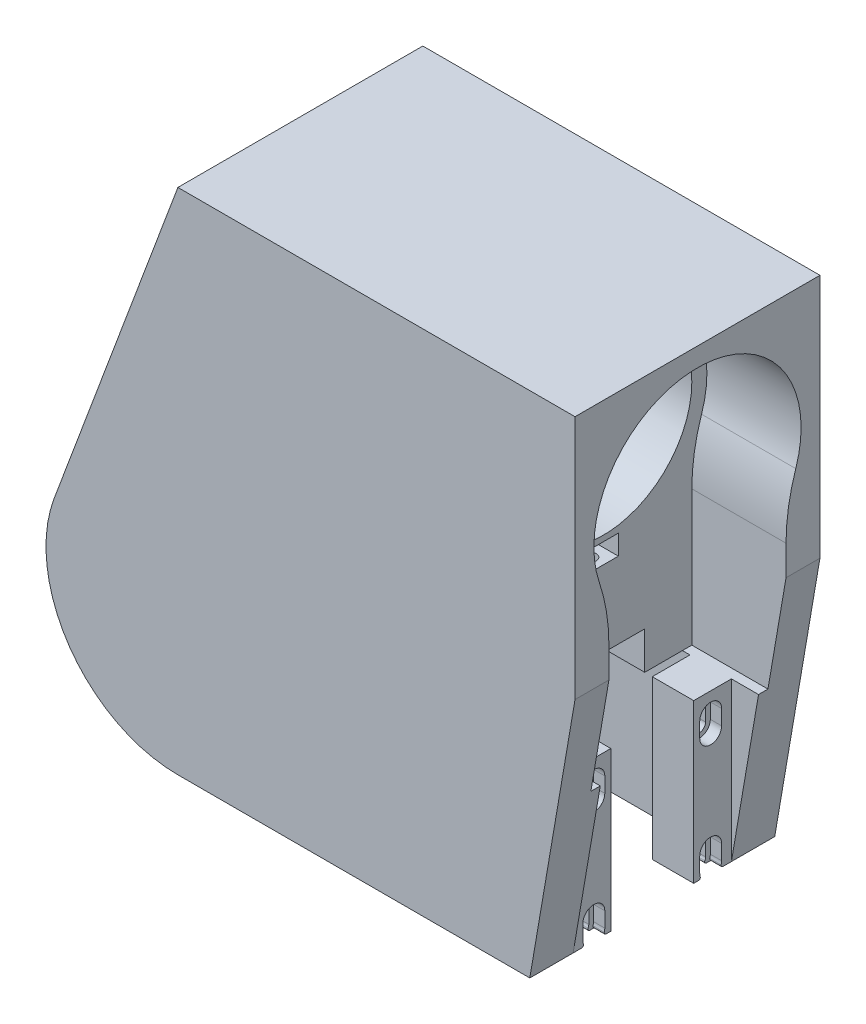
SolidWorks part; units mm, degrees
ref_plane "Ebene vorne" through (0, 0, 0) normal (0, 0, 1) x (1, 0, 0)
ref_plane "Ebene oben" through (0, 0, 0) normal (0, 1, 0) x (1, 0, 0)
ref_plane "Ebene rechts" through (0, 0, 0) normal (1, 0, 0) x (0, 0, -1)
sketch "Skizze1" plane through (0, 0, 0) normal (0, 0, 1) x (1, 0, 0)
  line L0 (0, -35) -> (6.4333, -35) construction
  line L1 (0, -35) -> (40.3912, -35)
  line L2 (82.3912, -35) -> (40.3912, -35)
  line L3 (82.3912, -35) -> (82.3912, 7)
  line L4 (82.3912, 7) -> (40.3912, 7)
  line L5 (40.3912, -35) -> (40.3912, 7)
  line L6 (82.3912, -35) -> (40.3912, 7) construction
  line L7 (82.3912, 7) -> (40.3912, -35) construction
  line L8 (40.3912, -35) -> (82.3912, -35)
  line L9 (40.3912, -35) -> (40.3912, -26.8814)
  line L12 (82.3912, -35) -> (93.3912, -35)
  line L14 (105.3912, 35) -> (93.3912, -35)
  line L15 (82.3912, 7) -> (0, 7)
  line L16 (82.3912, 7) -> (82.3912, 35)
  line L17 (82.3912, 35) -> (0, 35)
  line L18 (0, 7) -> (0, 35)
  line L19 (82.3912, 7) -> (0, 35) construction
  line L20 (82.3912, 35) -> (0, 7) construction
  line L21 (0, 35) -> (105.3912, 35)
  line L22 (0, 35) -> (0, 100)
  line L23 (0, 100) -> (105.3912, 100)
  line L24 (105.3912, 35) -> (105.3912, 100)
  line L25 (0, 35) -> (105.3912, 100) construction
  line L26 (0, 100) -> (105.3912, 35) construction
  line L27 (82.3912, 35) -> (93.3912, 35)
  line L28 (82.3912, 35) -> (82.3912, -35)
  line L30 (93.3912, 35) -> (93.3912, -35)
  line L31 (82.3912, 35) -> (93.3912, -35) construction
  line L32 (88.7388, -5.3941) -> (93.3912, 35) construction
  line L33 (0, 100) -> (-32.7862, 12.25)
  line L35 (105.3912, 35) -> (71.3912, 35)
  line L36 (105.3912, 35) -> (105.3912, 100)
  line L37 (105.3912, 100) -> (71.3912, 100)
  line L38 (71.3912, 35) -> (71.3912, 100)
  line L39 (105.3912, 35) -> (71.3912, 100) construction
  line L40 (105.3912, 100) -> (71.3912, 35) construction
  circle A0 centre (0, 0) radius 35
  point P10 (61.3912, -23.5)
  point P15 (41.1956, 21)
  point P19 (52.6956, 67.5)
  point P22 (88.7388, -5.3941)
  point P26 (88.3912, 67.5)
  dimension "D1" = 70
  dimension "D2" = 42
  dimension "D3" = 42
  dimension "D4" = 11
  dimension "D5" = 65
  dimension "D6" = 12
  dimension "D8" = 34
extrude "Aufsatz-Linear austragen1" add sketch "Skizze1" along normal blind 65
sketch "Skizze2" plane through (105.3912, 0, 0) normal (1, 0, 0) x (0, 0, -1)
  line L0 (-32.5, 100) -> (-32.5, -35) construction
  line L1 (-65, 100) -> (0, 100) construction
  line L4 (-53.5, 7) -> (-11.5, 7)
  line L5 (-53.5, 7) -> (-53.5, -35)
  line L6 (-53.5, -35) -> (-11.5, -35)
  line L7 (-11.5, 7) -> (-11.5, -35)
  line L8 (-53.5, 7) -> (-11.5, -35) construction
  line L9 (-53.5, -35) -> (-11.5, 7) construction
  line L13 (-65, -35) -> (0, -35) construction
  point P6 (-32.5, -14)
  dimension "D1" = 42
  dimension "D3" = 42
extrude "Schnitt-Linear austragen1" cut sketch "Skizze2" against normal up to vertex (12 mm away)
sketch "Skizze3" plane through (105.3912, 0, 0) normal (1, 0, 0) x (0, 0, -1)
  line L0 (0, 35) -> (0, 100) construction
  line L1 (-65, 100) -> (0, 100)
  line L2 (-65, 100) -> (-65, 35)
  line L3 (-65, 35) -> (0, 35)
  line L4 (0, 100) -> (0, 35)
  line L5 (-65, 100) -> (0, 35) construction
  line L6 (-65, 35) -> (0, 100) construction
  line L7 (0, 35) -> (0, -35) construction
  circle A0 centre (-32.5, 67.5) radius 15
  point P4 (-32.5, 67.5)
  dimension "D1" = 30
extrude "Schnitt-Linear austragen2" cut sketch "Skizze3" against normal blind 147 contours A0
ref_plane "Ebene1" through (-20.6088, 0, 0) normal (-1, 0, 0) x (0, 0, 1)
sketch "Skizze5" plane through (-20.6088, 0, 0) normal (-1, 0, 0) x (0, 0, 1)
  circle A0 centre (32.5, 67.5) radius 23.5
  dimension "D1" = 47
extrude "Schnitt-Linear austragen3" cut sketch "Skizze5" against normal blind 46 and the other way blind 3
sketch "Skizze6" plane through (25.3912, 0, 0) normal (-1, 0, 0) x (0, 0, 1)
  circle A0 centre (32.5, 67.5) radius 20
  dimension "D1" = 40
extrude "Schnitt-Linear austragen4" cut sketch "Skizze6" against normal blind 5
sketch "Skizze8" plane through (105.3912, 0, 0) normal (1, 0, 0) x (0, 0, -1)
  circle A0 centre (-32.5, 67.5) radius 23.5
  dimension "D1" = 47
extrude "Schnitt-Linear austragen5" cut sketch "Skizze8" against normal blind 37
sketch "Skizze9" plane through (68.3912, 0, 0) normal (1, 0, 0) x (0, 0, -1)
  circle A0 centre (-32.5, 67.5) radius 20
  dimension "D1" = 40
extrude "Schnitt-Linear austragen6" cut sketch "Skizze9" against normal blind 5
sketch "Skizze10" plane through (0, 0, 0) normal (0, 0, -1) x (-1, 0, 0)
  circle A0 centre (0, 0) radius 15
  circle A1 centre (0, 0) radius 7
  dimension "D1" = 30
  dimension "D2" = 14
extrude "Schnitt-Linear austragen7" cut sketch "Skizze10" against normal offset from surface (47.5 mm away) 17.5 contours A1 up to face at (43.1708, 28.112, 65)
sketch "Skizze11" plane through (0, 100, 0) normal (0, 1, 0) x (1, 0, 0)
  line L1 (7, -17.5) -> (-7, -17.5)
  line L2 (7, -17.5) -> (7, -47.5)
  line L3 (7, -47.5) -> (-7, -47.5)
  line L4 (-7, -17.5) -> (-7, -47.5)
  line L5 (7, -17.5) -> (-7, -47.5) construction
  line L6 (7, -47.5) -> (-7, -17.5) construction
  line L7 (0, -65) -> (0, 0) construction
  point P4 (0, -32.5)
  point P8 (0, -32.5)
  dimension "D1" = 14
  dimension "D2" = 30
extrude "Schnitt-Linear austragen8" cut sketch "Skizze11" against normal blind 65 from offset 34 offset against normal yes
ref_plane "Ebene2" through (-35, 0, 0) normal (-1, 0, 0) x (0, 0, 1)
sketch "Skizze12" plane through (-35, 0, 0) normal (-1, 0, 0) x (0, 0, 1)
  line L0 (32.5, 67.5) -> (32.5, -35) construction
  line L2 (65, -35) -> (0, -35) construction
  line L3 (9.75, 11.25) -> (55.25, 11.25)
  line L4 (9.75, 11.25) -> (9.75, -11.25)
  line L5 (9.75, -11.25) -> (55.25, -11.25)
  line L6 (55.25, 11.25) -> (55.25, -11.25)
  line L7 (9.75, 11.25) -> (55.25, -11.25) construction
  line L8 (9.75, -11.25) -> (55.25, 11.25) construction
  point P5 (32.5, 0)
  dimension "D1" = 22.5
  dimension "D2" = 45.5
extrude "Schnitt-Linear austragen9" cut sketch "Skizze12" against normal blind 4
sketch "Skizze13" plane through (-31, 0, 0) normal (-1, 0, 0) x (0, 0, 1)
  line L0 (9.75, 11.25) -> (55.25, 11.25) construction
  line L1 (17.5, 8.75) -> (47.5, 8.75)
  line L2 (17.5, 8.75) -> (17.5, -8.75)
  line L3 (17.5, -8.75) -> (47.5, -8.75)
  line L4 (47.5, 8.75) -> (47.5, -8.75)
  line L5 (17.5, 8.75) -> (47.5, -8.75) construction
  line L6 (17.5, -8.75) -> (47.5, 8.75) construction
  point P0 (32.5, 0)
  point P9 (32.5, 11.25)
  dimension "D1" = 30
  dimension "D2" = 17.5
extrude "Schnitt-Linear austragen10" cut sketch "Skizze13" against normal blind 31
sketch "Skizze14" plane through (105.3912, 0, 0) normal (1, 0, 0) x (0, 0, -1)
  line L0 (-11.5, 7) -> (-53.5, 7) construction
  line L1 (-56, 67.5) -> (-9, 67.5)
  line L2 (-56, 67.5) -> (-56, 7)
  line L3 (-56, 7) -> (-9, 7)
  line L4 (-9, 67.5) -> (-9, 7)
  line L5 (-56, 67.5) -> (-9, 7) construction
  line L6 (-56, 7) -> (-9, 67.5) construction
  circle A0 centre (-32.5, 67.5) radius 23.5 construction
  circle A1 centre (-32.5, 67.5) radius 23.5 construction
  point P4 (-32.5, 37.25)
extrude "Schnitt-Linear austragen11" cut sketch "Skizze14" against normal offset from surface (25 mm away) 12 up to face at (68.3912, 67.5, 12.5)
sketch "Skizze19" plane through (93.3912, 0, 0) normal (1, 0, 0) x (0, 0, -1)
  line L1 (-53.5, 7) -> (-11.5, 7)
  line L2 (-53.5, 7) -> (-53.5, -35)
  line L3 (-53.5, -35) -> (-11.5, -35)
  line L4 (-11.5, 7) -> (-11.5, -35)
  line L5 (-53.5, 7) -> (-11.5, -35) construction
  line L6 (-53.5, -35) -> (-11.5, 7) construction
  line L7 (-43.5, -35) -> (-21.5, -35)
  line L8 (-43.5, -35) -> (-43.5, 7)
  line L9 (-43.5, 7) -> (-21.5, 7)
  line L10 (-21.5, -35) -> (-21.5, 7)
  line L11 (-43.5, -35) -> (-21.5, 7) construction
  line L12 (-43.5, 7) -> (-21.5, -35) construction
  point P4 (-32.5, -14)
  point P7 (-32.5, -14)
  dimension "D1" = 22
extrude "Schnitt-Linear austragen17" cut sketch "Skizze19" against normal blind 11 contours L3 L10 L1 L8
sketch "Skizze20" plane through (82.3912, 0, 0) normal (1, 0, 0) x (0, 0, -1)
  line L0 (-21.5, -35) -> (-21.5, 7) construction
  line L1 (-53.5, 7) -> (-11.5, 7)
  line L2 (-53.5, 7) -> (-53.5, -35)
  line L3 (-53.5, -35) -> (-11.5, -35)
  line L4 (-11.5, 7) -> (-11.5, -35)
  line L5 (-53.5, 7) -> (-11.5, -35) construction
  line L6 (-53.5, -35) -> (-11.5, 7) construction
  line L7 (-43.5, 7) -> (-21.5, 7)
  line L8 (-43.5, 7) -> (-43.5, 17)
  line L9 (-43.5, 17) -> (-21.5, 17)
  line L10 (-21.5, 7) -> (-21.5, 17)
  line L11 (-43.5, 7) -> (-21.5, 17) construction
  line L12 (-43.5, 17) -> (-21.5, 7) construction
  point P4 (-32.5, -14)
  point P11 (-32.5, 12)
  dimension "D1" = 10
extrude "Schnitt-Linear austragen18" cut sketch "Skizze20" against normal blind 40
sketch "Skizze21" plane through (42.3912, 0, 0) normal (1, 0, 0) x (0, 0, -1)
  line L1 (-43.5, 17) -> (-21.5, 17)
  line L2 (-43.5, 17) -> (-43.5, 7)
  line L3 (-43.5, 7) -> (-21.5, 7)
  line L4 (-21.5, 17) -> (-21.5, 7)
  line L5 (-43.5, 17) -> (-21.5, 7) construction
  line L6 (-43.5, 7) -> (-21.5, 17) construction
  point P4 (-32.5, 12)
extrude "Schnitt-Linear austragen19" cut sketch "Skizze21" against normal up to surface (35.3912 mm away) up to face at (7, 23.8525, 32.5)
sketch "Skizze22" plane through (93.3912, 0, 0) normal (1, 0, 0) x (0, 0, -1)
  line L0 (-48, 1.5) -> (-17, 1.5) construction
  line L1 (-53.5, 7) -> (-11.5, 7)
  line L2 (-53.5, 7) -> (-53.5, -35)
  line L3 (-53.5, -35) -> (-11.5, -35)
  line L4 (-11.5, 7) -> (-11.5, -35)
  line L5 (-53.5, 7) -> (-11.5, -35) construction
  line L6 (-53.5, -35) -> (-11.5, 7) construction
  line L7 (-48, 1.5) -> (-48, -2.5) construction
  line L8 (-46.35, 1.5) -> (-46.35, -2.5)
  line L9 (-49.65, 1.5) -> (-49.65, -2.5)
  line L10 (-32.5, -14) -> (-32.5, -10.696) construction
  line L11 (-17, 1.5) -> (-17, -2.5) construction
  line L12 (-18.65, 1.5) -> (-18.65, -2.5)
  line L13 (-15.35, 1.5) -> (-15.35, -2.5)
  line L14 (-49.65, -29.5) -> (-49.65, -33.5)
  line L15 (-46.35, -29.5) -> (-46.35, -33.5)
  line L16 (-18.65, -29.5) -> (-18.65, -33.5)
  line L17 (-15.35, -29.5) -> (-15.35, -33.5)
  line L18 (-48, -29.5) -> (-48, -33.5) construction
  line L19 (-17, -29.5) -> (-17, -33.5) construction
  arc A0 (-46.35, 1.5) -> (-49.65, 1.5) centre (-48, 1.5) ccw
  arc A1 (-49.65, -2.5) -> (-46.35, -2.5) centre (-48, -2.5) ccw
  arc A2 (-18.65, 1.5) -> (-15.35, 1.5) centre (-17, 1.5) cw
  arc A3 (-15.35, -2.5) -> (-18.65, -2.5) centre (-17, -2.5) cw
  arc A4 (-46.35, -29.5) -> (-49.65, -29.5) centre (-48, -29.5) ccw
  arc A5 (-49.65, -33.5) -> (-46.35, -33.5) centre (-48, -33.5) ccw
  arc A6 (-15.35, -33.5) -> (-18.65, -33.5) centre (-17, -33.5) cw
  arc A7 (-18.65, -29.5) -> (-15.35, -29.5) centre (-17, -29.5) cw
  point P4 (-32.5, -14)
  point P9 (-48, -0.5)
  point P18 (-17, -0.5)
  point P27 (-48, -31.5)
  point P34 (-17, -31.5)
  dimension "D2" = 2
  dimension "D1" = 31
extrude "Schnitt-Linear austragen20" cut sketch "Skizze22" against normal up to surface (11 mm away) contours L9 A1 L8 A0 | A3 L13 A2 L12 | A7 L16 A6 L3 L17 | L14 A5 L3 L15 A4
sketch "Skizze23" plane through (93.3912, 0, 0) normal (1, 0, 0) x (0, 0, -1)
  line L0 (-48, 1.5) -> (-48, -2.5) construction
  line L1 (-45.1, 1.5) -> (-45.1, -2.5)
  line L2 (-50.9, 1.5) -> (-50.9, -2.5)
  line L3 (-32.5, 7) -> (-32.5, -35) construction
  line L5 (-53.5, -35) -> (-11.5, -35) construction
  line L6 (-17, 1.5) -> (-17, -2.5) construction
  line L7 (-19.9, 1.5) -> (-19.9, -2.5)
  line L8 (-14.1, 1.5) -> (-14.1, -2.5)
  line L9 (-50.9, -29.5) -> (-50.9, -33.5)
  line L10 (-45.1, -29.5) -> (-45.1, -33.5)
  line L11 (-19.9, -29.5) -> (-19.9, -33.5)
  line L12 (-14.1, -29.5) -> (-14.1, -33.5)
  line L13 (-48, -29.5) -> (-48, -33.5) construction
  line L14 (-17, -29.5) -> (-17, -33.5) construction
  line L15 (-43.5, 7) -> (-21.5, 7) construction
  arc A0 (-45.1, 1.5) -> (-50.9, 1.5) centre (-48, 1.5) ccw
  arc A1 (-50.9, -2.5) -> (-45.1, -2.5) centre (-48, -2.5) ccw
  arc A2 (-19.9, 1.5) -> (-14.1, 1.5) centre (-17, 1.5) cw
  arc A3 (-14.1, -2.5) -> (-19.9, -2.5) centre (-17, -2.5) cw
  arc A4 (-45.1, -29.5) -> (-50.9, -29.5) centre (-48, -29.5) ccw
  arc A5 (-50.9, -33.5) -> (-45.1, -33.5) centre (-48, -33.5) ccw
  arc A6 (-14.1, -33.5) -> (-19.9, -33.5) centre (-17, -33.5) cw
  arc A7 (-19.9, -29.5) -> (-14.1, -29.5) centre (-17, -29.5) cw
  point P4 (-48, -0.5)
  point P17 (-17, -0.5)
  point P22 (0, 0)
  point P26 (-48, -31.5)
  point P33 (-17, -31.5)
  dimension "D1" = 2
extrude "Schnitt-Linear austragen21" cut sketch "Skizze23" against normal blind 3
fillet "Verrundung2" radius 0.5 8 edges at (86.3912, -35, 47.3126) (86.3912, -35, 48.6874) (86.3912, -35, 16.3126) (86.3912, -35, 17.6874) (91.8912, -35, 45.5181) (91.8912, -35, 50.4819) (91.8912, -35, 14.5181) (91.8912, -35, 19.4819)
sketch "Skizze24" plane through (0, 0, 0) normal (0, 0, -1) x (-1, 0, 0)
  line L0 (0, 7) -> (0, 15) construction
  circle A0 centre (0, 0) radius 7
  circle A1 centre (0, 0) radius 15
  circle A2 centre (0, 11) radius 2.25
  circle A3 centre (11, 0) radius 2.25
  circle A4 centre (0, -11) radius 2.25
  circle A5 centre (-11, 0) radius 2.25
  point P20 (0, 0)
  dimension "D1" = 30
  dimension "D2" = 4.5
  dimension "D4" = 14
  dimension "D3" = 4
extrude "Schnitt-Linear austragen22" cut sketch "Skizze24" against normal blind 15
sketch "Skizze25" plane through (-31, 0, 0) normal (-1, 0, 0) x (0, 0, 1)
  line L0 (9.75, 7.2787) -> (16.75, 7.2787) construction
  line L1 (9.75, 11.2787) -> (55.25, 11.2787)
  line L2 (9.75, 11.2787) -> (9.75, -11.25)
  line L3 (9.75, -11.25) -> (55.25, -11.25)
  line L4 (55.25, 11.2787) -> (55.25, -11.25)
  line L5 (9.75, 11.2787) -> (55.25, -11.25) construction
  line L6 (9.75, -11.25) -> (55.25, 11.2787) construction
  line L8 (32.5, 0.0143) -> (32.5, 2.7471) construction
  line L9 (32.5, 2.7471) -> (32.5, 0.0143) construction
  line L10 (32.5, 0.0143) -> (28.5274, 0.0143) construction
  circle A0 centre (13.25, 7.2787) radius 2.25
  circle A1 centre (13.25, -7.25) radius 2.25
  circle A2 centre (51.75, -7.25) radius 2.25
  circle A3 centre (51.75, 7.2787) radius 2.25
  point P4 (32.5, 0.0143)
  point P9 (16.1306, 7.2787)
  point P10 (16.5813, 7.2787)
  point P22 (0, 0)
  point P23 (17, 7.2787)
  dimension "D1" = 4.5
  dimension "D2" = 4
  dimension "D3" = 3.5
extrude "Schnitt-Linear austragen23" cut sketch "Skizze25" against normal blind 5 contours A0 | A3 | A2 | A1
sketch "Skizze26" plane through (-32.7862, 12.25, 0) normal (-0.9367, 0.35, 0) x (0, 0, 1)
  line L0 (32.5, 46.8375) -> (32.5, 53.1519) construction
  line L1 (0, 93.675) -> (65, 93.675)
  line L2 (0, 93.675) -> (0, 0)
  line L3 (0, 0) -> (65, 0)
  line L4 (65, 93.675) -> (65, 0)
  line L5 (0, 93.675) -> (65, 0) construction
  line L6 (0, 0) -> (65, 93.675) construction
  line L7 (32.5, 53.1519) -> (32.5, 46.8375) construction
  line L8 (32.5, 46.8375) -> (26.0723, 46.8375) construction
  circle A0 centre (7.5, 85.8375) radius 2.2572
  circle A1 centre (57.5, 85.8375) radius 2.2572
  circle A2 centre (57.5, 7.8375) radius 2.2572
  circle A3 centre (7.5, 7.8375) radius 2.2572
  point P4 (32.5, 46.8375)
  point P18 (64.5, 0)
  point P19 (0, 0)
  point P21 (0, 0)
  dimension "D1" = 39
  dimension "D2" = 7.5
  dimension "D3" = 93.675
  dimension "D4" = 65
  dimension "D6" = 50
extrude "Schnitt-Linear austragen24" cut sketch "Skizze26" against normal blind 5 contours A0 | A1 | A2 | A3
fillet "Verrundung4" radius 0.5 8 edges at (-1.9531, 94.7727, 57.5) (-3.5331, 90.5438, 7.5) (-29.2531, 21.7062, 7.5) (-30.8331, 17.4773, 57.5) (-31, -7.25, 54) (-31, 7.2787, 54) (-31, 7.2787, 15.5) (-31, -7.25, 15.5)
sketch "Skizze27" plane through (80.3912, 0, 0) normal (1, 0, 0) x (0, 0, -1)
  line L0 (-32.5, 44) -> (-24.5867, 44) construction
  line L1 (-24.5867, 44) -> (-40.6647, 44) construction
  line L3 (-36.5, 44) -> (-28.5, 44)
  line L4 (-36.5, 44) -> (-36.5, 42.5)
  line L5 (-36.5, 42.5) -> (-28.5, 42.5)
  line L6 (-28.5, 44) -> (-28.5, 42.5)
  line L7 (-36.5, 44) -> (-28.5, 42.5) construction
  line L8 (-36.5, 42.5) -> (-28.5, 44) construction
  line L9 (-36.5, 42.5) -> (-28.5, 42.5)
  line L10 (-36.5, 42.5) -> (-36.5, 37.2)
  line L11 (-36.5, 37.2) -> (-28.5, 37.2)
  line L12 (-28.5, 42.5) -> (-28.5, 37.2)
  line L13 (-36.5, 42.5) -> (-28.5, 37.2) construction
  line L14 (-36.5, 37.2) -> (-28.5, 42.5) construction
  circle A1 centre (-32.5, 67.5) radius 23.5 construction
  point P10 (-32.5, 43.25)
  point P16 (-32.5, 39.85)
  dimension "D1" = 1.5
  dimension "D2" = 8
  dimension "D3" = 5.3
extrude "Schnitt-Linear austragen25" cut sketch "Skizze27" against normal blind 14 contours L12 L5 L10 L11
sketch "Skizze28" plane through (66.3912, 0, 0) normal (1, 0, 0) x (0, 0, -1)
  line L0 (-36.5, 42.5) -> (-28.5, 42.5) construction
  line L1 (-36.5, 42.5) -> (-28.5, 42.5)
  line L2 (-36.5, 42.5) -> (-36.5, 37.2)
  line L3 (-36.5, 37.2) -> (-28.5, 37.2)
  line L4 (-28.5, 42.5) -> (-28.5, 37.2)
  line L5 (-36.5, 42.5) -> (-28.5, 37.2) construction
  line L6 (-36.5, 37.2) -> (-28.5, 42.5) construction
  line L7 (-36.5, 37.2) -> (-28.5, 37.2) construction
  line L9 (-35.15, 37.2) -> (-29.85, 37.2)
  line L10 (-35.15, 37.2) -> (-35.15, 42.5)
  line L11 (-35.15, 42.5) -> (-29.85, 42.5)
  line L12 (-29.85, 37.2) -> (-29.85, 42.5)
  line L13 (-35.15, 37.2) -> (-29.85, 42.5) construction
  line L14 (-35.15, 42.5) -> (-29.85, 37.2) construction
  point P4 (-32.5, 39.85)
  point P9 (-32.5, 39.85)
  dimension "D1" = 5.3
extrude "Schnitt-Linear austragen26" cut sketch "Skizze28" against normal blind 14 contours L3 L12 L1 L10
sketch "Skizze29" plane through (0, 37.2, 0) normal (0, 1, 0) x (1, 0, 0)
  line L0 (52.3912, -35.15) -> (66.3912, -35.15) construction
  line L1 (52.3912, -35.15) -> (60.3912, -35.15)
  line L2 (52.3912, -35.15) -> (52.3912, -29.85)
  line L3 (52.3912, -29.85) -> (60.3912, -29.85)
  line L4 (60.3912, -35.15) -> (60.3912, -29.85)
  line L5 (52.3912, -35.15) -> (60.3912, -29.85) construction
  line L6 (52.3912, -29.85) -> (60.3912, -35.15) construction
  line L7 (52.3912, -35.15) -> (52.3912, -29.85) construction
  point P4 (56.3912, -32.5)
  dimension "D1" = 8
extrude "Schnitt-Linear austragen27" cut sketch "Skizze29" against normal up to surface (20.2 mm away) up to face at (43.6956, 17, 32.5)
sketch "Skizze30" plane through (0, 17, 0) normal (0, -1, 0) x (1, 0, 0)
  line L0 (82.3912, 32.5) -> (76.8912, 32.5)
  line L1 (82.3912, 43.5) -> (82.3912, 21.5) construction
  circle A0 centre (76.8912, 32.5) radius 1.65
  dimension "D1" = 5.5
extrude "Schnitt-Linear austragen28" cut sketch "Skizze30" against normal up to surface (20.2 mm away) up to face at (68.3912, 37.2, 32.5)
sketch "Skizze31" plane through (0, 17, 0) normal (0, -1, 0) x (1, 0, 0)
  circle A0 centre (76.8912, 32.5) radius 3
  circle A1 centre (76.8912, 32.5) radius 1.65 construction
  dimension "D1" = 6
extrude "Schnitt-Linear austragen29" cut sketch "Skizze31" against normal offset from surface (13.2 mm away) 7 up to face at (76.8912, 37.2, 30.85)
fillet "Verrundung6" radius 8 1 edges at (52.3912, 42.5, 32.5)
sketch "Skizze32" plane through (105.3912, 0, 0) normal (1, 0, 0) x (0, 0, -1)
  circle A0 centre (-32.5, 67.5) radius 27.5
  dimension "D1" = 55
extrude "Schnitt-Linear austragen30" cut sketch "Skizze32" against normal up to surface (25 mm away) up to face at (80.3912, 18.75, 32.5)
sketch "Skizze33" plane through (0, 0, 0) normal (0, 0, -1) x (-1, 0, 0)
  line L1 (-35.617, -35) -> (-25.617, -35) construction
  line L3 (-35.617, -29) -> (-25.617, -29)
  line L4 (-35.617, -41) -> (-25.617, -41)
  line L5 (0, -35) -> (-93.3912, -35) construction
  arc A1 (-35.617, -29) -> (-35.617, -41) centre (-35.617, -35) ccw
  arc A2 (-25.617, -41) -> (-25.617, -29) centre (-25.617, -35) ccw
  point P4 (-30.617, -35)
  dimension "D1" = 10
  dimension "D2" = 12
extrude "Schnitt-Linear austragen31" cut sketch "Skizze33" against normal blind 5
fillet "Verrundung7" radius 1 12 edges at (-5.2915, 4.5826, 17.5) (6.9641, 1, 17.5) (0, -7, 32.5) (21.3744, -30.7574, 0) (30.617, -35, 5) (39.8597, -30.7574, 0) (30.617, -29, 0) (39.8597, -30.7574, 5) (41.617, -35, 2.5) (19.617, -35, 2.5) (21.3744, -30.7574, 5) (30.617, -29, 5)
fillet "Verrundung8" radius 50 2 edges at (92.8912, 53.2171, 9) (92.8912, 53.2171, 56)
